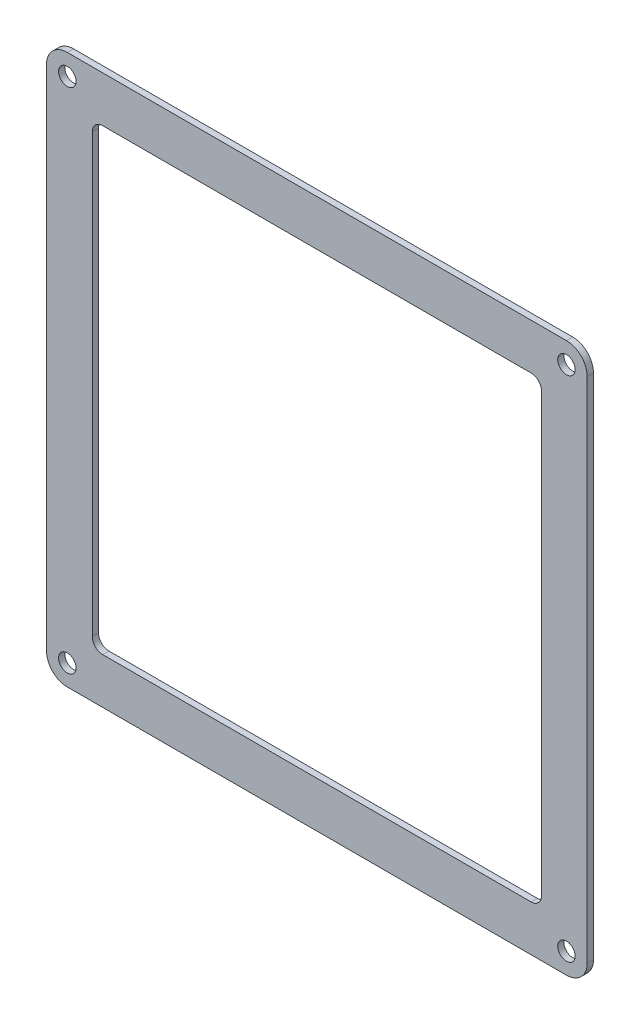
SolidWorks part; units mm, degrees
material "天然橡胶"
ref_plane "前视基准面" through (0, 0, 0) normal (0, 0, 1) x (1, 0, 0)
ref_plane "上视基准面" through (0, 0, 0) normal (0, 1, 0) x (1, 0, 0)
ref_plane "右视基准面" through (0, 0, 0) normal (1, 0, 0) x (0, 0, -1)
sketch "草图1" plane through (0, 0, 0) normal (0, 0, 1) x (1, 0, 0)
  line L1 (-108, -110.125) -> (108, -110.125)
  line L2 (-108, -110.125) -> (-108, 110.125)
  line L3 (-108, 110.125) -> (108, 110.125)
  line L4 (108, -110.125) -> (108, 110.125)
  line L5 (-108, -110.125) -> (108, 110.125) construction
  line L6 (-108, 110.125) -> (108, -110.125) construction
  line L7 (-130, -132.125) -> (130, -132.125)
  line L8 (-130, -132.125) -> (-130, 132.125)
  line L9 (-130, 132.125) -> (130, 132.125)
  line L10 (130, -132.125) -> (130, 132.125)
  line L11 (-130, -132.125) -> (130, 132.125) construction
  line L12 (-130, 132.125) -> (130, -132.125) construction
  point P0 (0, 0)
  point P6 (0, 0)
  dimension "D1" = 216
  dimension "D2" = 220.25
  dimension "D3" = 22
  dimension "D4" = 22
extrude "凸台-拉伸1" add sketch "草图1" along normal blind 3
fillet "圆角1" radius 10 4 edges at (130, 132.125, 1.5) (130, -132.125, 1.5) (-130, -132.125, 1.5) (-130, 132.125, 1.5)
fillet "圆角2" radius 5 4 edges at (-108, 110.125, 1.5) (-108, -110.125, 1.5) (108, -110.125, 1.5) (108, 110.125, 1.5)
hole_wizard "Ø8.4 (8.4) 直径孔1" positions "草图2" profile "草图3" hole size "Ø8.4" standard "GB" end condition through all
sketch "草图2" plane through (0, 0, 3) normal (0, 0, 1) x (1, 0, 0)
  point P0 (120, -122.125)
  point P3 (-120, 122.125)
  point P6 (-120, -122.125)
  point P9 (120, 122.125)
sketch "草图3" plane through (120, -122.125, 3) normal (1, 0, 0) x (0, -1, 0)
  line L0 (0, 0) -> (0, 3)
  line L1 (0, 3) -> (4.2, 3)
  line L2 (4.2, 3) -> (4.2, 0)
  line L5 (4.2, 0) -> (0, 0)
  line L11 (0, -6.35) -> (0, 107.95) construction
  dimension "通孔孔直径" = 8.4
  dimension "通孔孔深度" = 3
